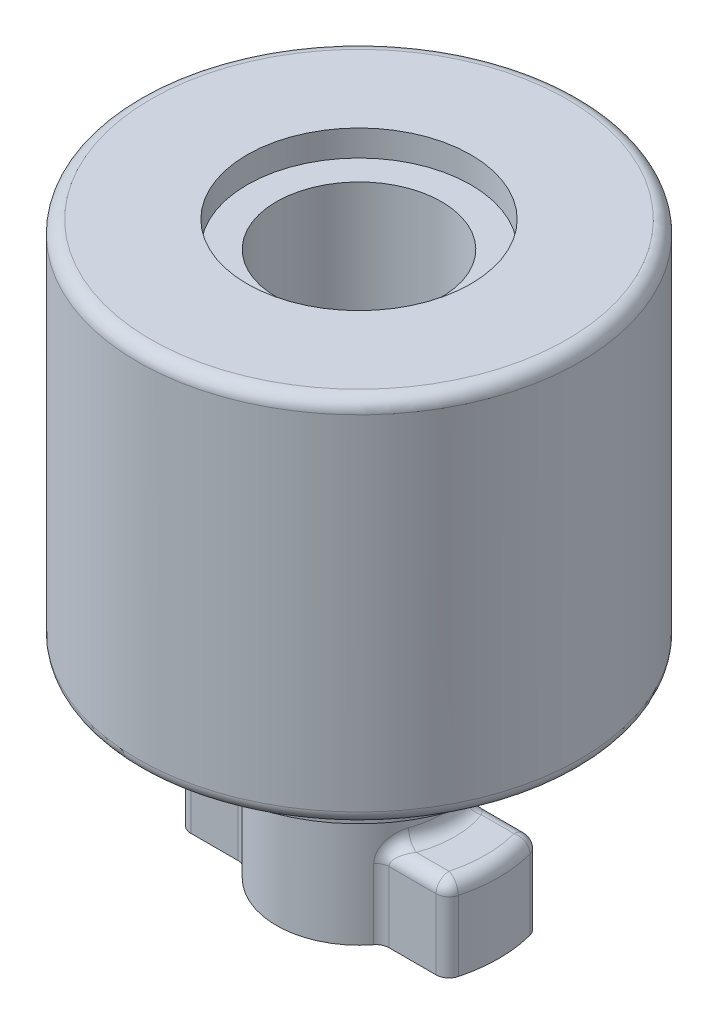
SolidWorks part; units mm, degrees
ref_plane "CL Y" through (0, 0, 0) normal (0, 0, 1) x (1, 0, 0)
ref_plane "Bottom" through (0, 0, 0) normal (0, 1, 0) x (1, 0, 0)
ref_plane "CL X " through (0, 0, 0) normal (1, 0, 0) x (0, 0, -1)
sketch "Sketch1" plane through (0, 0, 0) normal (0, 0, 1) x (1, 0, 0)
  line L0 (-8.5, 14.22) -> (-3.175, 14.22)
  line L1 (0, -50) -> (0, 50) construction
  line L2 (-8.5, 14.22) -> (-8.5, 0)
  line L3 (50, 0) -> (-50, 0) construction
  line L4 (-8.5, 0) -> (-5.66, 0)
  line L5 (-5.66, 0) -> (-5.66, -1.9)
  line L6 (-5.66, -1.9) -> (-3.175, -1.9)
  line L7 (-3.175, -1.9) -> (-3.175, -7.7)
  line L8 (-3.175, -7.7) -> (0, -7.7)
  line L9 (0, 3.04) -> (0, -7.7) construction
  line L10 (-6.7, -1.3) -> (-6.7, -4.2297) construction
  line L11 (-6.7, -1.3) -> (-5.39, -1.3) construction
  line L12 (-6.7, -2.61) -> (-5.1144, -2.61) construction
  line L13 (-9.3715, -2.4) -> (0.6009, -2.4) construction
  line L14 (-8.1323, -4.7) -> (4.6223, -4.7) construction
  line L15 (0, 3.04) -> (0, -7.7)
  line L16 (-3.175, 14.22) -> (-3.175, 3.04)
  line L17 (-3.175, 3.04) -> (0, 3.04)
  circle A0 centre (-6.7, -1.3) radius 1.31 construction
  dimension "D7" = 2.62
  dimension "D2" = 14.22
  dimension "D3" = 1.9
  dimension "D4" = 5.66
  dimension "D5" = 6.7
  dimension "D6" = 1.3
  dimension "D8" = 5.39
  dimension "D9" = 0.5
  dimension "D10" = 6.35
  dimension "D11" = 2.3
  dimension "D12" = 3
  dimension "D13" = 8.5
  dimension "11.18" = 11.18
  dimension "D14" = 3.175
revolve "Revolve1" add sketch "Sketch1" angle 360 about L15
sketch "Sketch2" plane through (0, -7.7, 0) normal (0, -1, 0) x (1, 0, 0)
  line L0 (-3.175, 0) -> (3.175, 0) construction
  line L1 (-5.375, 0) -> (6.9422, 0) construction
  line L2 (-5.0821, 1.75) -> (5.0821, 1.75)
  line L3 (0, 1.75) -> (0, -1.75) construction
  line L4 (-5.0821, -1.75) -> (5.0821, -1.75)
  circle A0 centre (0, 0) radius 3.175 construction
  circle A1 centre (0, 0) radius 3.175 construction
  arc A2 (-5.0821, 1.75) -> (-5.0821, -1.75) centre (0, 0) ccw
  arc A3 (5.0821, -1.75) -> (5.0821, 1.75) centre (0, 0) ccw
  dimension "D4" = 1.75
  dimension "D1" = 5.375
  dimension "D3" = 1.75
extrude "Boss-Extrude1" add sketch "Sketch2" against normal blind 3.2
fillet "Fillet1" radius 1.2 1 edges at (-5.66, 0, 0)
fillet "Fillet2" radius 0.5 18 edges at (2.6492, -6.1, 1.75) (3.175, -4.5, 0) (-2.6492, -6.1, -1.75) (-2.6492, -6.1, 1.75) (-8.5, 14.22, 0) (-8.5, 0, 0) (5.375, -4.5, 0) (5.0821, -6.1, -1.75) (3.8657, -4.5, -1.75) (2.6492, -6.1, -1.75) (-3.8657, -4.5, -1.75) (-5.0821, -6.1, -1.75) (-5.375, -4.5, 0) (3.8657, -4.5, 1.75) (-3.8657, -4.5, 1.75) (5.0821, -6.1, 1.75) (-5.0821, -6.1, 1.75) (-3.175, -4.5, 0)
sketch "Sketch4" plane through (0, 14.22, 0) normal (0, 1, 0) x (1, 0, 0)
  circle A0 centre (0, 0) radius 4.3
  dimension "D1" = 8.6
extrude "Cut-Extrude1" cut sketch "Sketch4" against normal blind 1
sketch "Sketch5" plane through (0, 3.04, 0) normal (0, 1, 0) x (1, 0, 0)
  circle A0 centre (0, 0) radius 1.5
  dimension "D1" = 3
extrude "Cut-Extrude2" cut sketch "Sketch5" against normal up to surface (10.74 mm away) up to face at (0, -7.7, 0)
